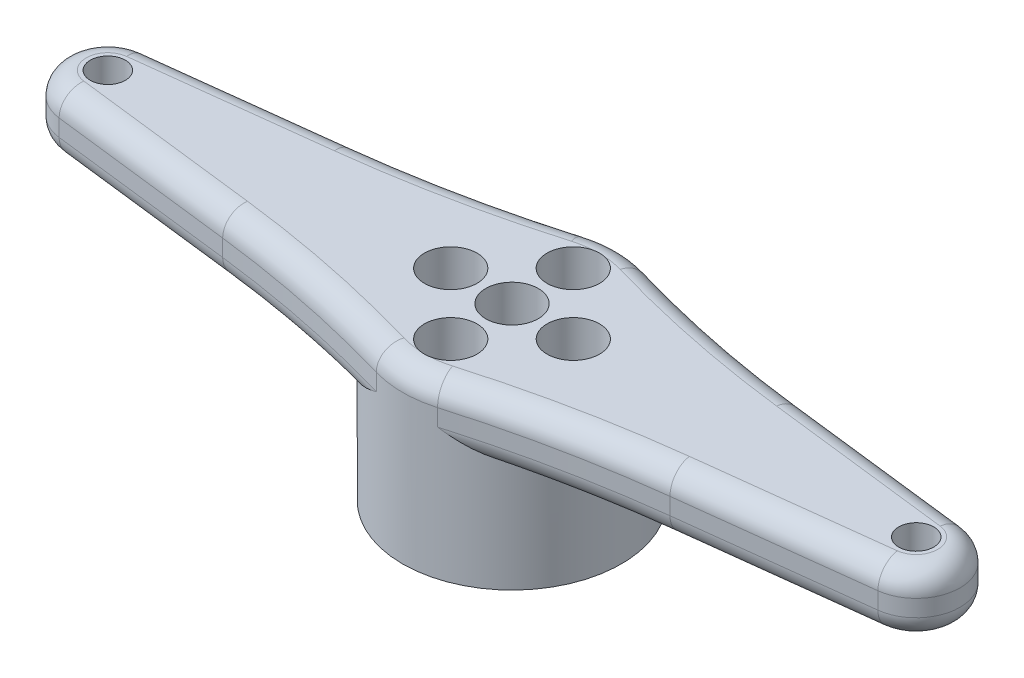
SolidWorks part; units mm, degrees
material "PLA"
ref_plane "Front Plane" through (0, 0, 0) normal (0, 0, 1) x (1, 0, 0)
ref_plane "Top Plane" through (0, 0, 0) normal (0, 1, 0) x (1, 0, 0)
ref_plane "Right Plane" through (0, 0, 0) normal (1, 0, 0) x (0, 0, -1)
sketch "Sketch1" plane through (0, 0, 0) normal (0, 1, 0) x (1, 0, 0)
  line L0 (0, 7) -> (0, 0) construction
  line L1 (0, 0) -> (0, 3) construction
  circle A0 centre (0, 0) radius 12.5
  circle A1 centre (0, 0) radius 3
  circle A2 centre (0, 7) radius 1.75
  circle A3 centre (7, 0) radius 1.75
  circle A4 centre (0, -7) radius 1.75
  circle A5 centre (-7, 0) radius 1.75
  point P15 (0, 0)
  dimension "D1" = 6
  dimension "D2" = 25
  dimension "D4" = 3.5
  dimension "D5" = 7
  dimension "D6" = 0
  dimension "D3" = 4
extrude "Boss-Extrude1" add sketch "Sketch1" along normal blind 15
sketch "Sketch2" plane through (0, 0, 0) normal (0, -1, 0) x (1, 0, 0)
  circle A7 centre (0, 0) radius 12.5
  circle A8 centre (0, 0) radius 10
  circle A9 centre (0, 0) radius 12.5 construction
  dimension "D1" = 20
extrude "Boss-Extrude2" add sketch "Sketch2" along normal blind 4.5
sketch "Sketch3" plane through (0, 15, 0) normal (0, 1, 0) x (1, 0, 0)
  line L0 (-46.7556, 4.9647) -> (-25.5434, 7.5)
  line L1 (-46.7556, -4.9647) -> (-25.5434, -7.5)
  arc A0 (-46.7556, 4.9647) -> (-46.7556, -4.9647) centre (-46.1623, 0) ccw
  arc A1 (-25.5434, 7.5) -> (-3.5, 12) centre (-41.7597, 143.176) ccw
  circle A2 centre (0, 0) radius 12.5 construction
  arc A3 (-25.5434, -7.5) -> (-3.5, -12) centre (-41.7597, -143.176) cw
  arc A4 (-3.5, 12) -> (-3.5, -12) centre (0, 0) ccw
  circle A5 centre (-46.1623, 0) radius 2
  dimension "D2" = 4
  dimension "D3" = 5
  dimension "D1" = 24
  dimension "D4" = 46.1623
  dimension "D5" = 15
extrude "Boss-Extrude3" add sketch "Sketch3" against normal blind 7
mirror "Mirror1" about plane through (0, 0, 0) normal (1, 0, 0) of "Boss-Extrude3"
fillet "Fillet1" radius 2.54 22 edges at (-36.1495, 15, 6.2323) (-51.1623, 15, 0) (-36.1495, 15, -6.2323) (-14.4289, 15, -9.2955) (0, 15, -12.5) (14.4289, 15, -9.2955) (36.1495, 15, -6.2323) (51.1623, 15, 0) (36.1495, 15, 6.2323) (14.4289, 15, 9.2955) (0, 15, 12.5) (-14.4289, 15, 9.2955) (14.4289, 8, -9.2955) (14.4289, 8, 9.2955) (36.1495, 8, 6.2323) (51.1623, 8, 0) (-14.4289, 8, -9.2955) (-14.4289, 8, 9.2955) (-36.1495, 8, 6.2323) (-51.1623, 8, 0) (36.1495, 8, -6.2323) (-36.1495, 8, -6.2323)
ref_plane "Plane1" through (0, 2.5, 0) normal (0, -1, 0) x (-1, 0, 0)
sketch "Sketch4" plane through (0, 2.5, 0) normal (0, 1, 0) x (1, 0, 0)
  circle A0 centre (0, 7) radius 3
  circle A1 centre (7, 0) radius 3
  circle A2 centre (0, -7) radius 3
  circle A3 centre (-7, 0) radius 3
  dimension "D1" = 6
extrude "Cut-Extrude1" cut sketch "Sketch4" along normal through all
